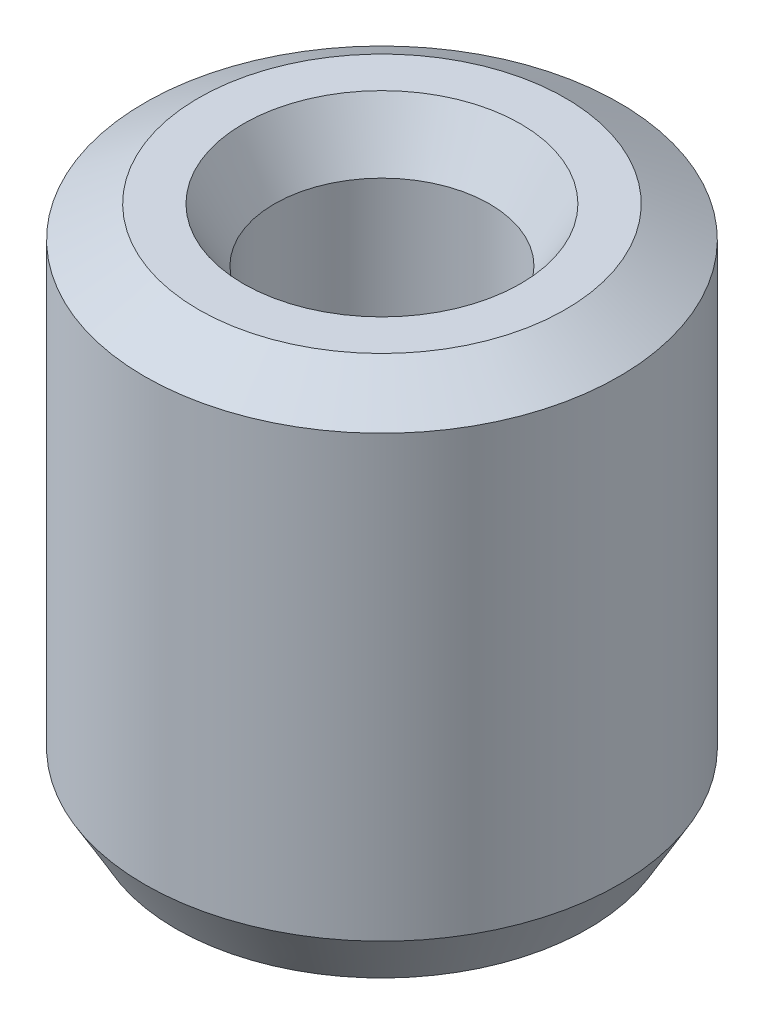
SolidWorks part; units mm, degrees
ref_plane "Front Plane" through (0, 0, 0) normal (0, 0, 1) x (1, 0, 0)
ref_plane "Top Plane" through (0, 0, 0) normal (0, 1, 0) x (1, 0, 0)
ref_plane "Right Plane" through (0, 0, 0) normal (1, 0, 0) x (0, 0, -1)
sketch "Sketch1" plane through (0, 0, 0) normal (0, 1, 0) x (1, 0, 0)
  circle A0 centre (0, 0) radius 7.5
  dimension "SLEEVE_OD" = 15
extrude "Boss-Extrude1" add sketch "Sketch1" along normal blind 16.5951
sketch "Sketch2" plane through (0, 0, 0) normal (0, 1, 0) x (1, 0, 0)
  circle A0 centre (0, 0) radius 3.4
  dimension "BORE_D" = 6.8001
extrude "Cut-Extrude1" cut sketch "Sketch2" along normal through all
chamfer "Chamfer1" distance 0.9824 angle 60 4 edges at (0, 16.5951, 3.4) (0, 0, 3.4) (0, 0, 7.5) (0, 16.5951, 7.5) first distance on face at (0, 16.5951, 3.4) first distance on face at (0, 0, 3.4) first distance on face at (0, 16.5951, 7.5)
